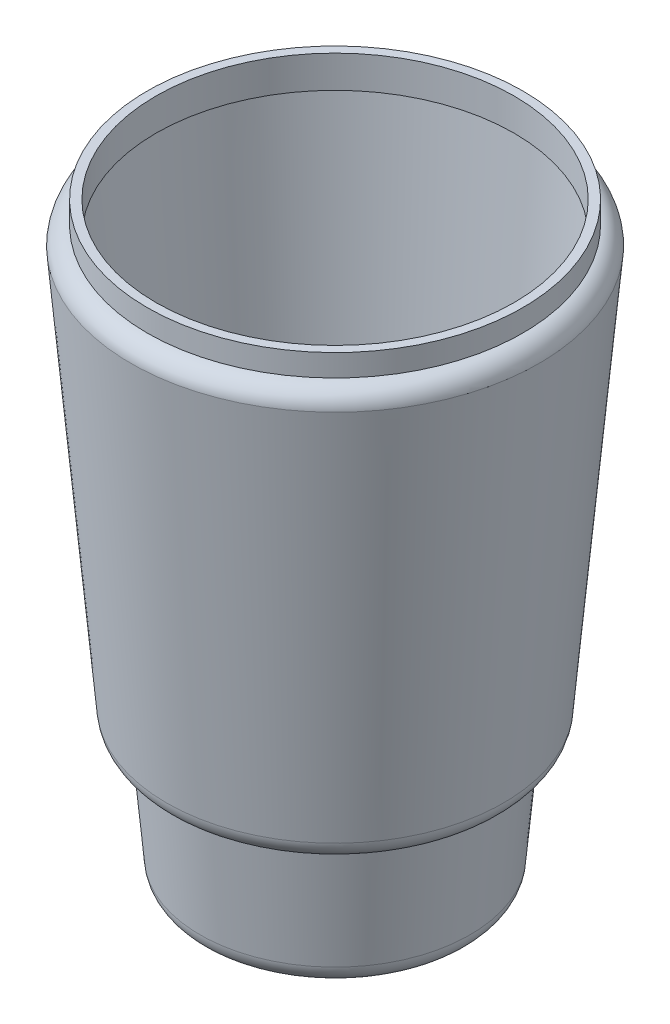
SolidWorks part; units mm, degrees
ref_plane "Front Plane" through (0, 0, 0) normal (0, 0, 1) x (1, 0, 0)
ref_plane "Top Plane" through (0, 0, 0) normal (0, 1, 0) x (1, 0, 0)
ref_plane "Right Plane" through (0, 0, 0) normal (1, 0, 0) x (0, 0, -1)
sketch "Sketch1" plane through (0, 0, 0) normal (1, 0, 0) x (0, 0, -1)
  line L0 (0, 0) -> (0, 135) construction
  line L1 (0, 0) -> (25.9265, 0)
  line L2 (0, 0) -> (0, 135)
  line L3 (33.1786, 30) -> (33.6051, 30)
  line L4 (38.5853, 34.5553) -> (46.7326, 125.8052)
  line L5 (43, 135) -> (43, 129.952)
  line L6 (33.1786, 30) -> (30.9067, 4.5553)
  line L7 (43, 135) -> (0, 135)
  arc A0 (33.6051, 30) -> (38.5853, 34.5553) centre (33.6051, 35) ccw
  arc A1 (43, 129.952) -> (46.7326, 125.8052) centre (42.3125, 125.5799) cw
  arc A2 (25.9265, 0) -> (30.9067, 4.5553) centre (25.9265, 5) ccw
  point P11 (38.1786, 30)
  point P15 (30.5, 0)
  dimension "D8" = 5
  dimension "D4" = 5
  dimension "D1" = 135
  dimension "D2" = 30.5
  dimension "D3" = 43
  dimension "D5" = 30
  dimension "D6" = 5
  dimension "D7" = 99.952
revolve "Revolve1" add sketch "Sketch1" angle 360 about L2
shell "Shell1" thickness 2 removed face at (0, 135, -43)
